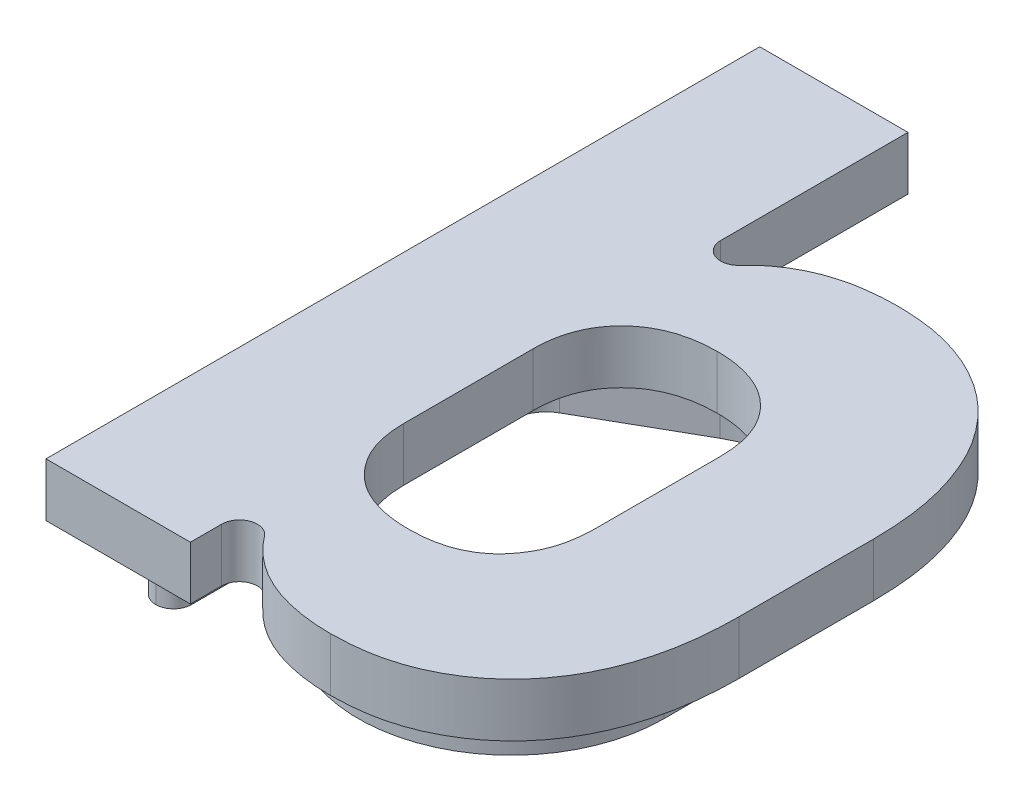
SolidWorks part; units mm, degrees
material "Красное дерево"
ref_plane "Спереди" through (0, 0, 0) normal (0, 0, 1) x (1, 0, 0)
ref_plane "Сверху" through (0, 0, 0) normal (0, 1, 0) x (1, 0, 0)
ref_plane "Справа" through (0, 0, 0) normal (1, 0, 0) x (0, 0, -1)
sketch "Эскиз b" plane through (0, 0, 0) normal (0, 1, 0) x (1, 0, 0)
  line L0 (0, 200) -> (41.5444, 200)
  line L1 (41.5444, 200) -> (41.5444, 147.5019)
  line L3 (135.4146, 96.4343) -> (135.4146, 58.8141)
  line L5 (40.4626, 8.7551) -> (40.4626, 0)
  line L6 (40.4626, 0) -> (0, 0)
  line L7 (0, 0) -> (0, 200)
  line L8 (93.9081, 60.016) -> (93.9081, 94.9519)
  line L9 (41.5444, 94.9519) -> (41.5444, 58.6138)
  line L10 (0, -24.9193) -> (0, 221.7067) construction
  line L11 (-26.4652, 0) -> (175.2563, 0) construction
  arc A0 (41.5444, 147.5019) -> (50.2847, 144.1838) centre (46.5444, 147.5019) ccw
  arc A1 (49.4869, 11.7225) -> (40.4626, 8.7551) centre (45.4626, 8.7551) ccw
  spline S2 degree 3 poles (50.2847, 144.1838) (50.4667, 144.3889) (51.3395, 145.3456) (53.0349, 146.9784) (55.5142, 148.9211) (58.1964, 150.6994) (61.1082, 152.21) (64.1748, 153.5515) (67.4504, 154.5623) (70.8771, 155.4462) (75.8304, 156.1473) (79.6485, 156.4337) (82.2495, 156.4103) knots 0.335543 0.335543 0.335543 0.335543 0.351035 0.408678 0.468317 0.52881 0.590251 0.653473 0.717675 0.783752 0.853236 1 1 1 1
  spline S3 degree 3 poles (82.2495, 156.4103) (86.12, 156.3503) (91.8434, 155.977) (99.1079, 154.1477) (104.1309, 152.3066) (108.8363, 149.9663) (113.2249, 147.202) (117.2699, 143.9634) (120.9612, 140.2655) (124.287, 136.1265) (127.2421, 131.5758) (129.7088, 126.5729) (131.795, 121.1992) (133.4356, 115.4608) (135.0073, 107.2042) (135.3941, 100.786) (135.4146, 96.4343) knots 0 0 0 0 0.128788 0.189121 0.248183 0.306088 0.363292 0.420078 0.477771 0.536427 0.59608 0.657554 0.72129 0.787255 0.855435 1 1 1 1
  spline S4 degree 3 poles (135.4146, 58.8141) (135.3883, 54.3034) (135.0181, 47.671) (133.4382, 39.1609) (131.8091, 33.3112) (129.7089, 27.8746) (127.2328, 22.8249) (124.2869, 18.2042) (120.9761, 13.9837) (117.2576, 10.2469) (113.2301, 6.924) (108.838, 4.0847) (104.1433, 1.6529) (99.1087, -0.2189) (91.8501, -2.1047) (86.1235, -2.5283) (82.2495, -2.5641) knots 0 0 0 0 0.147997 0.217046 0.28345 0.346798 0.407897 0.467542 0.52615 0.583432 0.64006 0.697021 0.754598 0.813074 0.872761 1 1 1 1
  spline S5 degree 3 poles (82.2495, -2.5641) (79.649, -2.5917) (75.818, -2.3128) (70.8805, -1.465) (67.4407, -0.5695) (64.173, 0.5415) (61.0957, 1.9519) (58.1806, 3.5879) (55.5118, 5.5316) (53.017, 7.6325) (51.0319, 9.7311) (49.9177, 11.1382) (49.4869, 11.7225) knots 0 0 0 0 0.141704 0.208996 0.272941 0.335358 0.396958 0.457301 0.517326 0.57673 0.634944 0.674514 0.674514 0.674514 0.674514
  spline S6 degree 3 poles (41.5444, 58.6138) (41.5695, 55.2564) (42.2708, 50.2259) (45.3176, 44.3512) (48.358, 40.5764) (52.2159, 37.4627) (58.6568, 34.4686) (64.1233, 33.7033) (67.8665, 33.734) knots 0 0 0 0 0.24798 0.363834 0.482443 0.601818 0.724705 1 1 1 1
  spline S7 degree 3 poles (67.8665, 33.734) (71.5967, 33.7231) (77.1104, 34.4147) (83.4487, 37.6377) (87.2412, 40.8681) (90.2035, 44.8488) (93.2535, 51.0903) (93.852, 56.4481) (93.9081, 60.016) knots 0 0 0 0 0.268987 0.38851 0.505395 0.623022 0.742123 1 1 1 1
  spline S8 degree 3 poles (93.9081, 94.9519) (93.8959, 98.4923) (93.228, 103.7674) (90.0615, 109.8203) (86.913, 113.5199) (83.0602, 116.506) (76.7854, 119.4201) (71.4862, 120.1613) (67.8665, 120.1122) knots 0 0 0 0 0.261299 0.379584 0.496338 0.615056 0.734226 1 1 1 1
  spline S9 degree 3 poles (67.8665, 120.1122) (64.2376, 120.1027) (58.892, 119.3824) (52.5583, 116.4352) (48.6496, 113.3844) (45.4435, 109.656) (42.317, 103.6157) (41.5035, 98.4483) (41.5444, 94.9519) knots 0 0 0 0 0.266055 0.387077 0.506835 0.626018 0.743974 1 1 1 1
  dimension "D3" = 10
  dimension "D4" = 10
  dimension "D1" = 40.4626
  dimension "D2" = 41.5444
extrude "b" add sketch "Эскиз b" along normal blind 15
sketch "Эскиз крепежа подсветки" plane through (0, 0, 0) normal (0, 1, 0) x (1, 0, 0)
  line L0 (20.77, 10) -> (20.77, 190)
  line L1 (34.8054, 34.0497) -> (57.9406, 20.729)
  line L2 (114.665, 53.5235) -> (114.665, 100.2754)
  line L3 (57.012, 133.7786) -> (20.77, 113.1261)
  arc A0 (57.9406, 20.729) -> (114.665, 53.5235) centre (76.8229, 53.5235) ccw
  arc A1 (114.665, 100.2754) -> (57.012, 133.7786) centre (76.1038, 100.2754) ccw
  dimension "D1" = 114.665
  dimension "D2" = 20.77
  dimension "D3" = 10
  dimension "D4" = 190
extrude "Крепёж подсветки" add sketch "Эскиз крепежа подсветки" against normal blind 15 thin thin type mid plane wall 10
fillet "Внешнее скруглнеие под ленту" radius 5 6 edges at (37.3003, -7.5, -38.3828) (32.3105, -7.5, -29.7166) (25.77, -7.5, -10) (15.77, -7.5, -10) (15.77, -7.5, -190) (25.77, -7.5, -190)
fillet "Внутреннее скругление под ленту" radius 10 2 edges at (25.77, -7.5, -110.2205) (25.77, -7.5, -121.7302)
sketch "Эскиз разметки под шурупы" plane through (0, 0, 0) normal (0, 1, 0) x (1, 0, 0)
  circle A0 centre (20.77, 185) radius 1.5
  circle A1 centre (20.77, 15) radius 1.5
  circle A2 centre (114.665, 75) radius 1.5
  dimension "D1" = 3
  dimension "D2" = 3
  dimension "D3" = 3
  dimension "D4" = 20.77
  dimension "D6" = 15
  dimension "D8" = 93.895
  dimension "D9" = 60
  dimension "D5" = 170
extrude "Разметка под шурупы" cut sketch "Эскиз разметки под шурупы" against normal through all
equation "\"drill\"= 3мм"
equation "\"D1@Эскиз разметки под шурупы\" = \"drill\""
equation "\"D2@Эскиз разметки под шурупы\" = \"drill\""
equation "\"D3@Эскиз разметки под шурупы\" = \"drill\""
